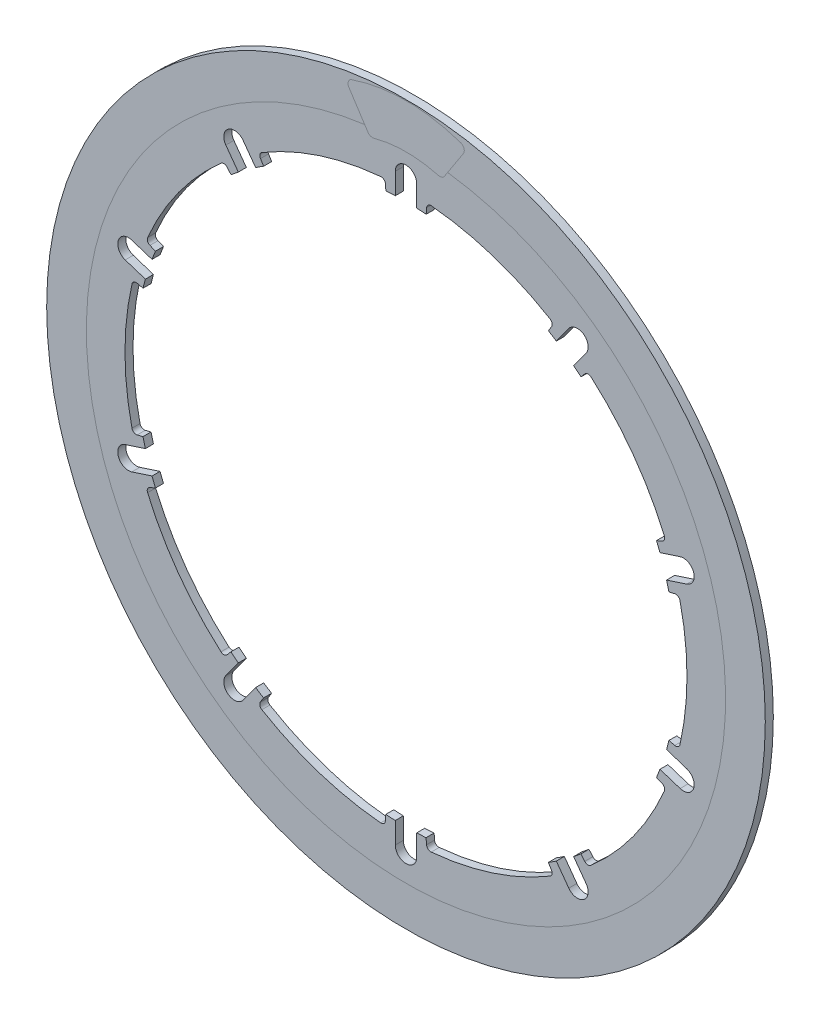
SolidWorks part; units mm, degrees
material "Gray Cast Iron"
ref_plane "Front Plane" through (0, 0, 0) normal (0, 0, 1) x (1, 0, 0)
ref_plane "Top Plane" through (0, 0, 0) normal (0, 1, 0) x (1, 0, 0)
ref_plane "Right Plane" through (0, 0, 0) normal (1, 0, 0) x (0, 0, -1)
sketch "Sketch1" plane through (0, 0, 0) normal (0, 0, 1) x (1, 0, 0)
  circle A0 centre (0, 0) radius 212.725
  dimension "D1" = 425.45
extrude "Boss-Extrude1" add sketch "Sketch1" along normal blind 4.7625
sketch3d "3DSketch3" [suppressed]
  line L4 (22.632, 184.3324, 30.7403) -> (33.9015, 201.686, 30.7403)
  line L5 (-33.9015, 201.686, 30.7403) -> (-22.632, 184.3324, 30.7403)
  arc A2 (-19.1346, 182.9983, 30.7403) -> (19.1346, 182.9983, 30.7403) centre (0, 112.7617, 30.7403) ccw
  spline S10 degree 3 poles (-22.632, 184.3324, 30.7403) (-22.5988, 184.2811, 30.7403) (-22.5293, 184.1805, 30.7403) (-22.4165, 184.0361, 30.7403) (-22.2957, 183.8983, 30.7403) (-22.1669, 183.7678, 30.7403) (-22.0309, 183.6449, 30.7403) (-21.8881, 183.53, 30.7403) (-21.7389, 183.4235, 30.7403) (-21.5838, 183.3258, 30.7403) (-21.4233, 183.2372, 30.7403) (-21.258, 183.1581, 30.7403) (-21.0428, 183.0698, 30.7403) (-20.7737, 182.9843, 30.7403) (-20.4488, 182.9172, 30.7403) (-20.1187, 182.8844, 30.7403) (-19.7871, 182.8865, 30.7403) (-19.4572, 182.9221, 30.7403) (-19.2411, 182.9691, 30.7403) (-19.1346, 182.9983, 30.7403) knots 0 0 0 0 0.045782 0.091558 0.137334 0.183113 0.228892 0.274672 0.32045 0.366227 0.412004 0.457782 0.503559 0.586301 0.669039 0.751777 0.834518 0.917255 1 1 1 1
  spline S11 degree 3 poles (19.1346, 182.9983, 30.7403) (19.1932, 182.9822, 30.7403) (19.3112, 182.9536, 30.7403) (19.4903, 182.9212, 30.7403) (19.6709, 182.8988, 30.7403) (19.8526, 182.8871, 30.7403) (20.0347, 182.8856, 30.7403) (20.2165, 182.8946, 30.7403) (20.3976, 182.9139, 30.7403) (20.5772, 182.9436, 30.7403) (20.7548, 182.9836, 30.7403) (20.9299, 183.0336, 30.7403) (21.1494, 183.1103, 30.7403) (21.4086, 183.2251, 30.7403) (21.6981, 183.3917, 30.7403) (21.9686, 183.5877, 30.7403) (22.2165, 183.8112, 30.7403) (22.4407, 184.059, 30.7403) (22.5716, 184.239, 30.7403) (22.632, 184.3324, 30.7403) knots 0 0 0 0 0.045473 0.090941 0.136409 0.181879 0.227351 0.272822 0.318291 0.36376 0.409229 0.454698 0.500168 0.583473 0.666777 0.750082 0.83339 0.916693 1 1 1 1
  spline S12 degree 3 poles (33.9015, 201.686, 30.7403) (33.9344, 201.7364, 30.7403) (33.9971, 201.839, 30.7403) (34.0817, 201.9976, 30.7403) (34.1575, 202.1609, 30.7403) (34.2237, 202.3283, 30.7403) (34.2804, 202.4992, 30.7403) (34.3274, 202.6731, 30.7403) (34.3646, 202.8492, 30.7403) (34.3917, 203.0273, 30.7403) (34.4086, 203.2065, 30.7403) (34.4153, 203.3864, 30.7403) (34.4119, 203.5665, 30.7403) (34.3756, 204.0435, 30.7403) (34.1614, 204.8075, 30.7403) (33.6821, 205.4852, 30.7403) (33.2752, 205.8566, 30.7403) (33.0454, 206.0314, 30.7403) (32.8006, 206.1843, 30.7403) (32.5436, 206.3149, 30.7403) (32.3643, 206.3858, 30.7403) (32.2732, 206.417, 30.7403) knots 0 0 0 0 0.031297 0.062588 0.093878 0.12517 0.156463 0.187756 0.219048 0.250339 0.28163 0.312921 0.344212 0.375504 0.562427 0.749344 0.799474 0.849606 0.899737 0.949865 1 1 1 1
  spline S13 degree 3 poles (32.2732, 206.417, 30.7403) (31.9592, 206.5252, 30.7403) (31.3303, 206.7384, 30.7403) (30.3838, 207.0486, 30.7403) (29.4343, 207.3495, 30.7403) (28.4817, 207.6406, 30.7403) (27.5262, 207.9222, 30.7403) (26.568, 208.1942, 30.7403) (25.6071, 208.4564, 30.7403) (24.6436, 208.7091, 30.7403) (23.6776, 208.952, 30.7403) (22.7092, 209.1852, 30.7403) (21.7385, 209.4087, 30.7403) (20.7656, 209.6224, 30.7403) (19.7906, 209.8263, 30.7403) (18.8136, 210.0204, 30.7403) (17.8348, 210.2046, 30.7403) (16.8541, 210.3791, 30.7403) (15.8717, 210.5436, 30.7403) (14.8877, 210.6982, 30.7403) (13.9022, 210.843, 30.7403) (12.9153, 210.9778, 30.7403) (11.927, 211.1027, 30.7403) (9.4532, 211.3901, 30.7403) (5.4798, 211.7206, 30.7403) (0, 211.8722, 30.7403) (-5.4798, 211.7206, 30.7403) (-9.7842, 211.3626, 30.7403) (-12.9159, 210.9828, 30.7403) (-14.8884, 210.7032, 30.7403) (-16.8549, 210.384, 30.7403) (-18.8146, 210.0253, 30.7403) (-20.7667, 209.6273, 30.7403) (-22.7103, 209.1901, 30.7403) (-24.6448, 208.7139, 30.7403) (-26.5694, 208.1991, 30.7403) (-28.483, 207.645, 30.7403) (-30.3853, 207.0535, 30.7403) (-31.6453, 206.6334, 30.7403) (-32.2732, 206.417, 30.7403) knots 0 0 0 0 0.015151 0.030302 0.045452 0.060603 0.075754 0.090905 0.106056 0.121206 0.136357 0.151508 0.166659 0.18181 0.19696 0.212111 0.227262 0.242413 0.257563 0.272714 0.287865 0.303016 0.318167 0.333317 0.41666 0.500002 0.583344 0.666687 0.696988 0.727289 0.75759 0.787892 0.818193 0.848494 0.878795 0.909096 0.939398 0.969699 1 1 1 1
  spline S14 degree 3 poles (-32.2732, 206.417, 30.7403) (-32.33, 206.3976, 30.7403) (-32.4424, 206.3554, 30.7403) (-32.6063, 206.2826, 30.7403) (-32.7663, 206.2007, 30.7403) (-32.9213, 206.1097, 30.7403) (-33.071, 206.0102, 30.7403) (-33.2148, 205.9024, 30.7403) (-33.3523, 205.7867, 30.7403) (-33.4831, 205.6634, 30.7403) (-33.6067, 205.5329, 30.7403) (-33.7226, 205.3956, 30.7403) (-33.8307, 205.2519, 30.7403) (-34.0967, 204.8533, 30.7403) (-34.3994, 204.1174, 30.7403) (-34.4385, 203.2861, 30.7403) (-34.346, 202.7423, 30.7403) (-34.2724, 202.4636, 30.7403) (-34.1736, 202.193, 30.7403) (-34.0515, 201.9325, 30.7403) (-33.9541, 201.7665, 30.7403) (-33.9015, 201.686, 30.7403) knots 0 0 0 0 0.031241 0.062476 0.093711 0.124947 0.156184 0.187421 0.218658 0.249893 0.281128 0.312363 0.343599 0.374835 0.562326 0.749809 0.799846 0.849885 0.899924 0.949958 1 1 1 1
  point P8 (0, 112.7617, -42.0561)
sketch "Sketch4" plane through (0, 0, 4.7625) normal (0, 0, 1) x (1, 0, 0)
  line L2 (22.7365, 184.6731) -> (34.006, 202.0267)
  line L3 (-33.7971, 202.0267) -> (-22.5275, 184.6731)
  arc A1 (19.2391, 183.339) -> (-19.0302, 183.339) centre (0.1045, 113.1023) ccw
  spline S5 degree 3 poles (34.006, 202.0267) (34.0389, 202.0771) (34.1016, 202.1797) (34.1862, 202.3383) (34.262, 202.5016) (34.3282, 202.669) (34.4038, 202.8969) (34.46, 203.1306) (34.4962, 203.3679) (34.5131, 203.5472) (34.5198, 203.7271) (34.5163, 203.9072) (34.4801, 204.3842) (34.2659, 205.1481) (33.7866, 205.8259) (33.3797, 206.1973) (33.1498, 206.3721) (32.9051, 206.525) (32.648, 206.6556) (32.4688, 206.7265) (32.3776, 206.7577) knots 0 0 0 0 0.031297 0.062588 0.093878 0.12517 0.156463 0.219048 0.250339 0.28163 0.312921 0.344212 0.375504 0.562427 0.749344 0.799474 0.849606 0.899737 0.949865 1 1 1 1
  spline S6 degree 3 poles (19.2391, 183.339) (19.2977, 183.3229) (19.4156, 183.2943) (19.5948, 183.2619) (19.7754, 183.2395) (19.9571, 183.2278) (20.1392, 183.2263) (20.321, 183.2353) (20.5021, 183.2546) (20.7416, 183.2942) (20.9771, 183.3543) (21.2539, 183.451) (21.5131, 183.5658) (21.8026, 183.7323) (22.073, 183.9284) (22.321, 184.1519) (22.5452, 184.3996) (22.6761, 184.5797) (22.7365, 184.6731) knots 0 0 0 0 0.045473 0.090941 0.136409 0.181879 0.227351 0.272822 0.318291 0.36376 0.454698 0.500168 0.583473 0.666777 0.750082 0.83339 0.916693 1 1 1 1
  spline S7 degree 3 poles (-22.5275, 184.6731) (-22.4943, 184.6218) (-22.4249, 184.5212) (-22.312, 184.3768) (-22.1912, 184.239) (-22.0624, 184.1085) (-21.9264, 183.9856) (-21.7836, 183.8707) (-21.6344, 183.7642) (-21.4276, 183.6339) (-21.2101, 183.5219) (-20.9383, 183.4105) (-20.6692, 183.325) (-20.3444, 183.2579) (-20.0142, 183.225) (-19.6827, 183.2272) (-19.3527, 183.2628) (-19.1367, 183.3098) (-19.0302, 183.339) knots 0 0 0 0 0.045782 0.091558 0.137334 0.183113 0.228892 0.274672 0.32045 0.366227 0.457782 0.503559 0.586301 0.669039 0.751777 0.834518 0.917255 1 1 1 1
  spline S8 degree 3 poles (-32.1687, 206.7577) (-32.2255, 206.7383) (-32.3379, 206.6961) (-32.5019, 206.6233) (-32.6618, 206.5414) (-32.8168, 206.4504) (-33.0164, 206.3177) (-33.2043, 206.1685) (-33.3786, 206.0041) (-33.5022, 205.8736) (-33.6182, 205.7363) (-33.7262, 205.5926) (-33.9922, 205.194) (-34.2949, 204.4581) (-34.3341, 203.6268) (-34.2415, 203.083) (-34.1679, 202.8043) (-34.0691, 202.5337) (-33.947, 202.2732) (-33.8496, 202.1072) (-33.7971, 202.0267) knots 0 0 0 0 0.031241 0.062476 0.093711 0.124947 0.156184 0.218658 0.249893 0.281128 0.312363 0.343599 0.374835 0.562326 0.749809 0.799846 0.849885 0.899924 0.949958 1 1 1 1
  spline S9 degree 3 poles (32.3776, 206.7577) (32.0637, 206.8659) (31.4348, 207.0791) (30.4883, 207.3893) (29.5388, 207.6902) (28.5862, 207.9813) (26.9938, 208.4506) (23.7904, 209.325) (20.2255, 210.1269) (16.6328, 210.7845) (14.6646, 211.0938) (13.0197, 211.3185) (12.0315, 211.4434) (9.5577, 211.7308) (5.5843, 212.0613) (0.1045, 212.2129) (-5.3753, 212.0613) (-9.6798, 211.7033) (-12.8114, 211.3235) (-14.7839, 211.0439) (-16.7504, 210.7247) (-18.7101, 210.366) (-20.6622, 209.968) (-22.6058, 209.5308) (-24.5403, 209.0546) (-26.4649, 208.5398) (-28.3785, 207.9857) (-30.2808, 207.3942) (-31.5409, 206.9741) (-32.1687, 206.7577) knots 0 0 0 0 0.015151 0.030302 0.045452 0.060603 0.075754 0.121206 0.212111 0.242413 0.287865 0.303016 0.318167 0.333317 0.41666 0.500002 0.583344 0.666687 0.696988 0.727289 0.75759 0.787892 0.818193 0.848494 0.878795 0.909096 0.939398 0.969699 1 1 1 1
sketch "Sketch8" plane through (0, 0, 0) normal (0, 0, -1) x (-1, 0, 0)
  circle A0 centre (0, 0) radius 166.37
  dimension "D1" = 332.74
extrude "Cut-Extrude1" cut sketch "Sketch8" against normal up to surface (4.7625 mm away) up to face at (212.725, 0, 4.7625)
sketch "Sketch9" plane through (0, 0, 0) normal (0, 0, -1) x (-1, 0, 0)
  line L1 (-6.35, 160.02) -> (6.35, 160.02)
  line L2 (-6.35, 160.02) -> (-6.35, 172.72)
  line L3 (-6.35, 172.72) -> (6.35, 172.72)
  line L4 (6.35, 160.02) -> (6.35, 172.72)
  line L5 (-6.35, 160.02) -> (6.35, 172.72) construction
  line L6 (-6.35, 172.72) -> (6.35, 160.02) construction
  circle A0 centre (0, 0) radius 166.37 construction
  circle A1 centre (0, 172.72) radius 6.35
  point P0 (0, 166.37)
  circle M4 centre (0, 0) radius 166.37
  dimension "D1" = 12.7
  dimension "D2" = 12.7
extrude "Cut-Extrude3" cut sketch "Sketch9" along direction (0, 0, 1) on the side against the normal up to surface (4.7625 mm away) contours L3 A1 | L3 A1 | A1 L4 M4 | A1 L2 M4 region at (4.9267, 167.7465, 0) region at (-4.9267, 167.7465, 0) region at (0, 175.415, 0) region at (0, 170.025, 0) up to face at (166.37, 0, 4.7625)
pattern_circular "CirPattern1" count 10 every 36 about axis through (0, 0, 0) along (0, 0, -1) of "Cut-Extrude3"
sketch "Sketch11" plane through (0, 0, 4.7625) normal (0, 0, 1) x (1, 0, 0)
  line L0 (-11.8938, 159.8321) -> (-12.1576, 163.3594)
  line L1 (-6.35, 166.2488) -> (-6.35, 160.1482)
  line L2 (6.35, 160.1482) -> (6.35, 166.2488)
  line L3 (11.9607, 159.8271) -> (12.2246, 163.3535)
  line L4 (6.35, 166.2488) -> (6.35, 172.72) construction
  arc A0 (11.9607, 159.8271) -> (6.35, 160.1482) centre (0, 0) ccw
  arc A1 (-6.35, 166.2488) -> (-92.5813, 138.2305) centre (0, 0) ccw construction
  arc A2 (92.5813, 138.2305) -> (6.35, 166.2488) centre (0, 0) ccw construction
  arc A3 (-6.35, 160.1482) -> (-11.8938, 159.8321) centre (0, 0) ccw
  arc A4 (-14.9183, 165.6998) -> (-92.5813, 138.2305) centre (0, 0) ccw
  arc A5 (92.5813, 138.2305) -> (14.9864, 165.6937) centre (0, 0) ccw
  arc A6 (-14.9183, 165.6998) -> (-12.1576, 163.3594) centre (-14.6905, 163.17) cw
  arc A7 (14.9864, 165.6937) -> (12.2246, 163.3535) centre (14.7576, 163.164) ccw
  arc M5 (-92.5813, 138.2305) -> (-6.35, 166.2488) centre (0, 0) cw
  arc M9 (6.35, 166.2488) -> (92.5813, 138.2305) centre (0, 0) cw
  dimension "D2" = 2.54
  dimension "D3" = 2.54
extrude "Boss-Extrude2" add sketch "Sketch11" against normal up to surface (4.7625 mm away) contours A0 L3 L2 M9 | A3 L1 L0 M5 region at (-9.3788, 163.1773, 4.7625) region at (9.4122, 163.1737, 4.7625) up to face at (0, 0, 0)
pattern_circular "CirPattern2" count 10 every 36 about axis through (0, 0, 4.7625) along (0, 0, -1) of "Boss-Extrude2"
sketch "Sketch15" [suppressed] plane through (0, 0, 6.35) normal (0, 0, 1) x (1, 0, 0)
  line L0 (-12.2165, 163.3739) -> (12.2261, 163.3732)
sketch "Sketch17" [suppressed] plane through (0, 0, 6.35) normal (0, 0, 1) x (1, 0, 0)
  line L0 (0, 0) -> (110.7699, 130.7089)
  line L1 (0, 0) -> (158.5451, 64.9479)
  arc A0 (161.9209, 73.4471) -> (119.8963, 131.2925) centre (0, 0) ccw
  arc A1 (161.9209, 73.4471) -> (158.5451, 64.9479) centre (156.138, 70.824) cw
  arc A2 (110.7699, 130.7089) -> (119.8963, 131.2925) centre (115.6143, 126.6035) cw
  dimension "D1" = 0
  dimension "D3" = 6.35
  dimension "D4" = 6.35
  dimension "D2" = 0
sketch "Sketch18" plane through (0, 0, 0) normal (0, 0, -1) x (-1, 0, 0)
  line L0 (33.7971, 202.0267) -> (22.5275, 184.6731) construction
  line L1 (-22.7365, 184.6731) -> (-34.006, 202.0267) construction
  line L2 (33.7971, 202.0267) -> (22.5275, 184.6731)
  line L3 (-22.7365, 184.6731) -> (-34.006, 202.0267)
  arc A0 (-24.6449, 187.6118) -> (24.4523, 187.637) centre (0, 0) ccw
  circle A1 centre (0, 0) radius 215.3351
  arc A2 (19.0302, 183.339) -> (-19.2391, 183.339) centre (-0.1045, 113.1023) ccw construction
  arc A3 (19.0302, 183.339) -> (-19.2391, 183.339) centre (-0.1045, 113.1023) ccw
  spline S0 degree 3 poles (-1450.1633, -1164.7301) (-59.0763, 285.4864) (32.2795, 197.129) (22.312, 184.3768) (22.1912, 184.239) (22.0624, 184.1085) (21.9264, 183.9856) (21.7836, 183.8707) (21.6344, 183.7642) (21.4276, 183.6339) (21.2101, 183.5219) (20.9383, 183.4105) (20.6692, 183.325) (20.3444, 183.2579) (20.0142, 183.225) (19.6827, 183.2272) (2.7527, 185.055) (8.5785, 322.4741) (2007.8128, 363.0309) knots -11.991769 -11.991769 -11.991769 -11.991769 0.045782 0.091558 0.137334 0.183113 0.228892 0.274672 0.32045 0.366227 0.457782 0.503559 0.586301 0.669039 0.751777 0.834518 0.917255 13.489507 13.489507 13.489507 13.489507 only from (22.5275, 184.6731) to (19.0302, 183.339) construction
  spline S1 degree 3 poles (-2016.3209, 153.4131) (-13.1774, 313.7756) (-3.6105, 186.1555) (-19.5948, 183.2619) (-19.7754, 183.2395) (-19.9571, 183.2278) (-20.1392, 183.2263) (-20.321, 183.2353) (-20.5021, 183.2546) (-20.7416, 183.2942) (-20.9771, 183.3543) (-21.2539, 183.451) (-21.5131, 183.5658) (-21.8026, 183.7323) (-22.073, 183.9284) (-22.321, 184.1519) (-33.7349, 196.7661) (61.8944, 295.2324) (1583.0626, -1002.353) knots -12.036429 -12.036429 -12.036429 -12.036429 0.045473 0.090941 0.136409 0.181879 0.227351 0.272822 0.318291 0.36376 0.454698 0.500168 0.583473 0.666777 0.750082 0.83339 0.916693 13.47468 13.47468 13.47468 13.47468 only from (-19.2391, 183.339) to (-22.7365, 184.6731) construction
  spline S2 degree 3 poles (-741.6985, 2071.3636) (51.5513, 215.3428) (-28.083, 190.8965) (-34.1862, 202.3383) (-34.262, 202.5016) (-34.3282, 202.669) (-34.4038, 202.8969) (-34.46, 203.1306) (-34.4962, 203.3679) (-34.5131, 203.5472) (-34.5198, 203.7271) (-34.5163, 203.9072) (-34.4801, 204.3842) (-34.2659, 205.1481) (-33.7866, 205.8259) (-33.3797, 206.1973) (-33.1498, 206.3721) (-32.9051, 206.525) (-19.4783, 213.3465) (41.9008, 122.514) (-1615.5521, -1012.0405) knots -6.679954 -6.679954 -6.679954 -6.679954 0.031297 0.062588 0.093878 0.12517 0.156463 0.219048 0.250339 0.28163 0.312921 0.344212 0.375504 0.562427 0.749344 0.799474 0.849606 0.899737 0.949865 8.706653 8.706653 8.706653 8.706653 only from (-34.006, 202.0267) to (-32.3776, 206.7577) construction
  spline S3 degree 3 poles (1661.243, 1259.3746) (-203.7859, -162.5293) (-163.0238, 163.9576) (-30.4883, 207.3893) (-29.5388, 207.6902) (-28.5862, 207.9813) (-26.9938, 208.4506) (-23.7904, 209.325) (-20.2255, 210.1269) (-16.6328, 210.7845) (-14.6646, 211.0938) (-13.0197, 211.3185) (-12.0315, 211.4434) (-9.5577, 211.7308) (-5.5843, 212.0613) (-0.1045, 212.2129) (5.3753, 212.0613) (9.6798, 211.7033) (12.8114, 211.3235) (14.7839, 211.0439) (16.7504, 210.7247) (18.7101, 210.366) (20.6622, 209.968) (22.6058, 209.5308) (24.5403, 209.0546) (26.4649, 208.5398) (28.3785, 207.9857) (189.3327, 157.9434) (218.1983, -304.2931) (-1891.4217, 643.6889) knots -6.319065 -6.319065 -6.319065 -6.319065 0.015151 0.030302 0.045452 0.060603 0.075754 0.121206 0.212111 0.242413 0.287865 0.303016 0.318167 0.333317 0.41666 0.500002 0.583344 0.666687 0.696988 0.727289 0.75759 0.787892 0.818193 0.848494 0.878795 0.909096 0.939398 0.969699 8.600273 8.600273 8.600273 8.600273 only from (-32.3776, 206.7577) to (32.1687, 206.7577) construction
  spline S4 degree 3 poles (1741.3262, -829.6052) (-26.9574, 143.7974) (20.6648, 211.8759) (32.5019, 206.6233) (32.6618, 206.5414) (32.8168, 206.4504) (33.0164, 206.3177) (33.2043, 206.1685) (33.3786, 206.0041) (33.5022, 205.8736) (33.6182, 205.7363) (33.7262, 205.5926) (33.9922, 205.194) (34.2949, 204.4581) (34.3341, 203.6268) (34.2415, 203.083) (34.1679, 202.8043) (34.0691, 202.5337) (27.687, 188.9067) (-76.4304, 222.6453) (533.1826, 2136.6237) knots -6.671073 -6.671073 -6.671073 -6.671073 0.031241 0.062476 0.093711 0.124947 0.156184 0.218658 0.249893 0.281128 0.312363 0.343599 0.374835 0.562326 0.749809 0.799846 0.849885 0.899924 0.949958 8.70048 8.70048 8.70048 8.70048 only from (32.1687, 206.7577) to (33.7971, 202.0267) construction
  spline S5 degree 3 poles (22.5275, 184.6731) (22.4943, 184.6218) (22.4249, 184.5212) (22.312, 184.3768) (22.1912, 184.239) (22.0624, 184.1085) (21.9264, 183.9856) (21.7836, 183.8707) (21.6344, 183.7642) (21.4276, 183.6339) (21.2101, 183.5219) (20.9383, 183.4105) (20.6692, 183.325) (20.3444, 183.2579) (20.0142, 183.225) (19.6827, 183.2272) (19.3527, 183.2628) (19.1367, 183.3098) (19.0302, 183.339) knots 0 0 0 0 0.045782 0.091558 0.137334 0.183113 0.228892 0.274672 0.32045 0.366227 0.457782 0.503559 0.586301 0.669039 0.751777 0.834518 0.917255 1 1 1 1
  spline S6 degree 3 poles (-19.2391, 183.339) (-19.2977, 183.3229) (-19.4156, 183.2943) (-19.5948, 183.2619) (-19.7754, 183.2395) (-19.9571, 183.2278) (-20.1392, 183.2263) (-20.321, 183.2353) (-20.5021, 183.2546) (-20.7416, 183.2942) (-20.9771, 183.3543) (-21.2539, 183.451) (-21.5131, 183.5658) (-21.8026, 183.7323) (-22.073, 183.9284) (-22.321, 184.1519) (-22.5452, 184.3996) (-22.6761, 184.5797) (-22.7365, 184.6731) knots 0 0 0 0 0.045473 0.090941 0.136409 0.181879 0.227351 0.272822 0.318291 0.36376 0.454698 0.500168 0.583473 0.666777 0.750082 0.83339 0.916693 1 1 1 1
  spline S7 degree 3 poles (-34.006, 202.0267) (-34.0389, 202.0771) (-34.1016, 202.1797) (-34.1862, 202.3383) (-34.262, 202.5016) (-34.3282, 202.669) (-34.4038, 202.8969) (-34.46, 203.1306) (-34.4962, 203.3679) (-34.5131, 203.5472) (-34.5198, 203.7271) (-34.5163, 203.9072) (-34.4801, 204.3842) (-34.2659, 205.1481) (-33.7866, 205.8259) (-33.3797, 206.1973) (-33.1498, 206.3721) (-32.9051, 206.525) (-32.648, 206.6556) (-32.4688, 206.7265) (-32.3776, 206.7577) knots 0 0 0 0 0.031297 0.062588 0.093878 0.12517 0.156463 0.219048 0.250339 0.28163 0.312921 0.344212 0.375504 0.562427 0.749344 0.799474 0.849606 0.899737 0.949865 1 1 1 1
  spline S8 degree 3 poles (-32.3776, 206.7577) (-32.0637, 206.8659) (-31.4348, 207.0791) (-30.4883, 207.3893) (-29.5388, 207.6902) (-28.5862, 207.9813) (-26.9938, 208.4506) (-23.7904, 209.325) (-20.2255, 210.1269) (-16.6328, 210.7845) (-14.6646, 211.0938) (-13.0197, 211.3185) (-12.0315, 211.4434) (-9.5577, 211.7308) (-5.5843, 212.0613) (-0.1045, 212.2129) (5.3753, 212.0613) (9.6798, 211.7033) (12.8114, 211.3235) (14.7839, 211.0439) (16.7504, 210.7247) (18.7101, 210.366) (20.6622, 209.968) (22.6058, 209.5308) (24.5403, 209.0546) (26.4649, 208.5398) (28.3785, 207.9857) (30.2808, 207.3942) (31.5409, 206.9741) (32.1687, 206.7577) knots 0 0 0 0 0.015151 0.030302 0.045452 0.060603 0.075754 0.121206 0.212111 0.242413 0.287865 0.303016 0.318167 0.333317 0.41666 0.500002 0.583344 0.666687 0.696988 0.727289 0.75759 0.787892 0.818193 0.848494 0.878795 0.909096 0.939398 0.969699 1 1 1 1
  spline S9 degree 3 poles (32.1687, 206.7577) (32.2255, 206.7383) (32.3379, 206.6961) (32.5019, 206.6233) (32.6618, 206.5414) (32.8168, 206.4504) (33.0164, 206.3177) (33.2043, 206.1685) (33.3786, 206.0041) (33.5022, 205.8736) (33.6182, 205.7363) (33.7262, 205.5926) (33.9922, 205.194) (34.2949, 204.4581) (34.3341, 203.6268) (34.2415, 203.083) (34.1679, 202.8043) (34.0691, 202.5337) (33.947, 202.2732) (33.8496, 202.1072) (33.7971, 202.0267) knots 0 0 0 0 0.031241 0.062476 0.093711 0.124947 0.156184 0.218658 0.249893 0.281128 0.312363 0.343599 0.374835 0.562326 0.749809 0.799846 0.849885 0.899924 0.949958 1 1 1 1
  dimension "D1" = 378.4471
  dimension "D2" = 430.6702
split line "Split Line3"
sketch "Sketch19" plane through (0, 0, 4.7625) normal (0, 0, 1) x (1, 0, 0)
  line L0 (-33.7971, 202.0267) -> (-22.5275, 184.6731) construction
  line L1 (22.7365, 184.6731) -> (34.006, 202.0267) construction
  line L2 (-33.7971, 202.0267) -> (-22.5275, 184.6731)
  line L3 (22.7365, 184.6731) -> (34.006, 202.0267)
  arc A0 (-24.4523, 187.637) -> (24.6449, 187.6118) centre (0, 0) ccw
  circle A1 centre (0, 0) radius 215.3351
  arc A2 (19.2391, 183.339) -> (-19.0302, 183.339) centre (0.1045, 113.1023) ccw construction
  arc A3 (19.2391, 183.339) -> (-19.0302, 183.339) centre (0.1045, 113.1023) ccw
  spline S0 degree 3 poles (1450.1633, -1164.7301) (59.0763, 285.4864) (-32.2795, 197.129) (-22.312, 184.3768) (-22.1912, 184.239) (-22.0624, 184.1085) (-21.9264, 183.9856) (-21.7836, 183.8707) (-21.6344, 183.7642) (-21.4276, 183.6339) (-21.2101, 183.5219) (-20.9383, 183.4105) (-20.6692, 183.325) (-20.3444, 183.2579) (-20.0142, 183.225) (-19.6827, 183.2272) (-2.7527, 185.055) (-8.5785, 322.4741) (-2007.8128, 363.0309) knots -11.991769 -11.991769 -11.991769 -11.991769 0.045782 0.091558 0.137334 0.183113 0.228892 0.274672 0.32045 0.366227 0.457782 0.503559 0.586301 0.669039 0.751777 0.834518 0.917255 13.489507 13.489507 13.489507 13.489507 only from (-22.5275, 184.6731) to (-19.0302, 183.339) construction
  spline S1 degree 3 poles (-1741.3262, -829.6052) (26.9574, 143.7974) (-20.6648, 211.8759) (-32.5019, 206.6233) (-32.6618, 206.5414) (-32.8168, 206.4504) (-33.0164, 206.3177) (-33.2043, 206.1685) (-33.3786, 206.0041) (-33.5022, 205.8736) (-33.6182, 205.7363) (-33.7262, 205.5926) (-33.9922, 205.194) (-34.2949, 204.4581) (-34.3341, 203.6268) (-34.2415, 203.083) (-34.1679, 202.8043) (-34.0691, 202.5337) (-27.687, 188.9067) (76.4304, 222.6453) (-533.1826, 2136.6237) knots -6.671073 -6.671073 -6.671073 -6.671073 0.031241 0.062476 0.093711 0.124947 0.156184 0.218658 0.249893 0.281128 0.312363 0.343599 0.374835 0.562326 0.749809 0.799846 0.849885 0.899924 0.949958 8.70048 8.70048 8.70048 8.70048 only from (-32.1687, 206.7577) to (-33.7971, 202.0267) construction
  spline S2 degree 3 poles (-1661.243, 1259.3746) (203.7859, -162.5293) (163.0238, 163.9576) (30.4883, 207.3893) (29.5388, 207.6902) (28.5862, 207.9813) (26.9938, 208.4506) (23.7904, 209.325) (20.2255, 210.1269) (16.6328, 210.7845) (14.6646, 211.0938) (13.0197, 211.3185) (12.0315, 211.4434) (9.5577, 211.7308) (5.5843, 212.0613) (0.1045, 212.2129) (-5.3753, 212.0613) (-9.6798, 211.7033) (-12.8114, 211.3235) (-14.7839, 211.0439) (-16.7504, 210.7247) (-18.7101, 210.366) (-20.6622, 209.968) (-22.6058, 209.5308) (-24.5403, 209.0546) (-26.4649, 208.5398) (-28.3785, 207.9857) (-189.3327, 157.9434) (-218.1983, -304.2931) (1891.4217, 643.6889) knots -6.319065 -6.319065 -6.319065 -6.319065 0.015151 0.030302 0.045452 0.060603 0.075754 0.121206 0.212111 0.242413 0.287865 0.303016 0.318167 0.333317 0.41666 0.500002 0.583344 0.666687 0.696988 0.727289 0.75759 0.787892 0.818193 0.848494 0.878795 0.909096 0.939398 0.969699 8.600273 8.600273 8.600273 8.600273 only from (32.3776, 206.7577) to (-32.1687, 206.7577) construction
  spline S3 degree 3 poles (741.6985, 2071.3636) (-51.5513, 215.3428) (28.083, 190.8965) (34.1862, 202.3383) (34.262, 202.5016) (34.3282, 202.669) (34.4038, 202.8969) (34.46, 203.1306) (34.4962, 203.3679) (34.5131, 203.5472) (34.5198, 203.7271) (34.5163, 203.9072) (34.4801, 204.3842) (34.2659, 205.1481) (33.7866, 205.8259) (33.3797, 206.1973) (33.1498, 206.3721) (32.9051, 206.525) (19.4783, 213.3465) (-41.9008, 122.514) (1615.5521, -1012.0405) knots -6.679954 -6.679954 -6.679954 -6.679954 0.031297 0.062588 0.093878 0.12517 0.156463 0.219048 0.250339 0.28163 0.312921 0.344212 0.375504 0.562427 0.749344 0.799474 0.849606 0.899737 0.949865 8.706653 8.706653 8.706653 8.706653 only from (34.006, 202.0267) to (32.3776, 206.7577) construction
  spline S4 degree 3 poles (2016.3209, 153.4131) (13.1774, 313.7756) (3.6105, 186.1555) (19.5948, 183.2619) (19.7754, 183.2395) (19.9571, 183.2278) (20.1392, 183.2263) (20.321, 183.2353) (20.5021, 183.2546) (20.7416, 183.2942) (20.9771, 183.3543) (21.2539, 183.451) (21.5131, 183.5658) (21.8026, 183.7323) (22.073, 183.9284) (22.321, 184.1519) (33.7349, 196.7661) (-61.8944, 295.2324) (-1583.0626, -1002.353) knots -12.036429 -12.036429 -12.036429 -12.036429 0.045473 0.090941 0.136409 0.181879 0.227351 0.272822 0.318291 0.36376 0.454698 0.500168 0.583473 0.666777 0.750082 0.83339 0.916693 13.47468 13.47468 13.47468 13.47468 only from (19.2391, 183.339) to (22.7365, 184.6731) construction
  spline S5 degree 3 poles (-22.5275, 184.6731) (-22.4943, 184.6218) (-22.4249, 184.5212) (-22.312, 184.3768) (-22.1912, 184.239) (-22.0624, 184.1085) (-21.9264, 183.9856) (-21.7836, 183.8707) (-21.6344, 183.7642) (-21.4276, 183.6339) (-21.2101, 183.5219) (-20.9383, 183.4105) (-20.6692, 183.325) (-20.3444, 183.2579) (-20.0142, 183.225) (-19.6827, 183.2272) (-19.3527, 183.2628) (-19.1367, 183.3098) (-19.0302, 183.339) knots 0 0 0 0 0.045782 0.091558 0.137334 0.183113 0.228892 0.274672 0.32045 0.366227 0.457782 0.503559 0.586301 0.669039 0.751777 0.834518 0.917255 1 1 1 1
  spline S6 degree 3 poles (-32.1687, 206.7577) (-32.2255, 206.7383) (-32.3379, 206.6961) (-32.5019, 206.6233) (-32.6618, 206.5414) (-32.8168, 206.4504) (-33.0164, 206.3177) (-33.2043, 206.1685) (-33.3786, 206.0041) (-33.5022, 205.8736) (-33.6182, 205.7363) (-33.7262, 205.5926) (-33.9922, 205.194) (-34.2949, 204.4581) (-34.3341, 203.6268) (-34.2415, 203.083) (-34.1679, 202.8043) (-34.0691, 202.5337) (-33.947, 202.2732) (-33.8496, 202.1072) (-33.7971, 202.0267) knots 0 0 0 0 0.031241 0.062476 0.093711 0.124947 0.156184 0.218658 0.249893 0.281128 0.312363 0.343599 0.374835 0.562326 0.749809 0.799846 0.849885 0.899924 0.949958 1 1 1 1
  spline S7 degree 3 poles (32.3776, 206.7577) (32.0637, 206.8659) (31.4348, 207.0791) (30.4883, 207.3893) (29.5388, 207.6902) (28.5862, 207.9813) (26.9938, 208.4506) (23.7904, 209.325) (20.2255, 210.1269) (16.6328, 210.7845) (14.6646, 211.0938) (13.0197, 211.3185) (12.0315, 211.4434) (9.5577, 211.7308) (5.5843, 212.0613) (0.1045, 212.2129) (-5.3753, 212.0613) (-9.6798, 211.7033) (-12.8114, 211.3235) (-14.7839, 211.0439) (-16.7504, 210.7247) (-18.7101, 210.366) (-20.6622, 209.968) (-22.6058, 209.5308) (-24.5403, 209.0546) (-26.4649, 208.5398) (-28.3785, 207.9857) (-30.2808, 207.3942) (-31.5409, 206.9741) (-32.1687, 206.7577) knots 0 0 0 0 0.015151 0.030302 0.045452 0.060603 0.075754 0.121206 0.212111 0.242413 0.287865 0.303016 0.318167 0.333317 0.41666 0.500002 0.583344 0.666687 0.696988 0.727289 0.75759 0.787892 0.818193 0.848494 0.878795 0.909096 0.939398 0.969699 1 1 1 1
  spline S8 degree 3 poles (34.006, 202.0267) (34.0389, 202.0771) (34.1016, 202.1797) (34.1862, 202.3383) (34.262, 202.5016) (34.3282, 202.669) (34.4038, 202.8969) (34.46, 203.1306) (34.4962, 203.3679) (34.5131, 203.5472) (34.5198, 203.7271) (34.5163, 203.9072) (34.4801, 204.3842) (34.2659, 205.1481) (33.7866, 205.8259) (33.3797, 206.1973) (33.1498, 206.3721) (32.9051, 206.525) (32.648, 206.6556) (32.4688, 206.7265) (32.3776, 206.7577) knots 0 0 0 0 0.031297 0.062588 0.093878 0.12517 0.156463 0.219048 0.250339 0.28163 0.312921 0.344212 0.375504 0.562427 0.749344 0.799474 0.849606 0.899737 0.949865 1 1 1 1
  spline S9 degree 3 poles (19.2391, 183.339) (19.2977, 183.3229) (19.4156, 183.2943) (19.5948, 183.2619) (19.7754, 183.2395) (19.9571, 183.2278) (20.1392, 183.2263) (20.321, 183.2353) (20.5021, 183.2546) (20.7416, 183.2942) (20.9771, 183.3543) (21.2539, 183.451) (21.5131, 183.5658) (21.8026, 183.7323) (22.073, 183.9284) (22.321, 184.1519) (22.5452, 184.3996) (22.6761, 184.5797) (22.7365, 184.6731) knots 0 0 0 0 0.045473 0.090941 0.136409 0.181879 0.227351 0.272822 0.318291 0.36376 0.454698 0.500168 0.583473 0.666777 0.750082 0.83339 0.916693 1 1 1 1
  dimension "D1" = 378.4471
  dimension "D2" = 430.6702
split line "Split Line4"
sketch "Sketch20" plane through (0, 0, 0) normal (0, 0, -1) x (-1, 0, 0)
  line L1 (-3.8126, 161.2345) -> (3.8319, 161.2345)
  line L2 (-3.8126, 161.2345) -> (-3.8126, 169.2274)
  line L3 (-3.8126, 169.2274) -> (-0.9809, 169.2274)
  line L4 (3.8319, 161.2345) -> (3.8319, 169.2274)
  line L5 (1.2675, 169.2274) -> (3.8319, 169.2274)
  line L7 (-0.9809, 169.2274) -> (-0.9809, 180.1204)
  line L8 (-0.9809, 180.1204) -> (1.2675, 180.1204)
  line L9 (1.2675, 169.2274) -> (1.2675, 180.1204)
  circle A0 centre (0, 165.1) radius 3.175
  dimension "D1" = 6.35
  dimension "D2" = 165.1
extrude "Boss-Extrude3" [suppressed] add sketch "Sketch20" against normal blind 0.0254
pattern_circular "CirPattern3" [suppressed] count 10 over 360 of bodies 117
